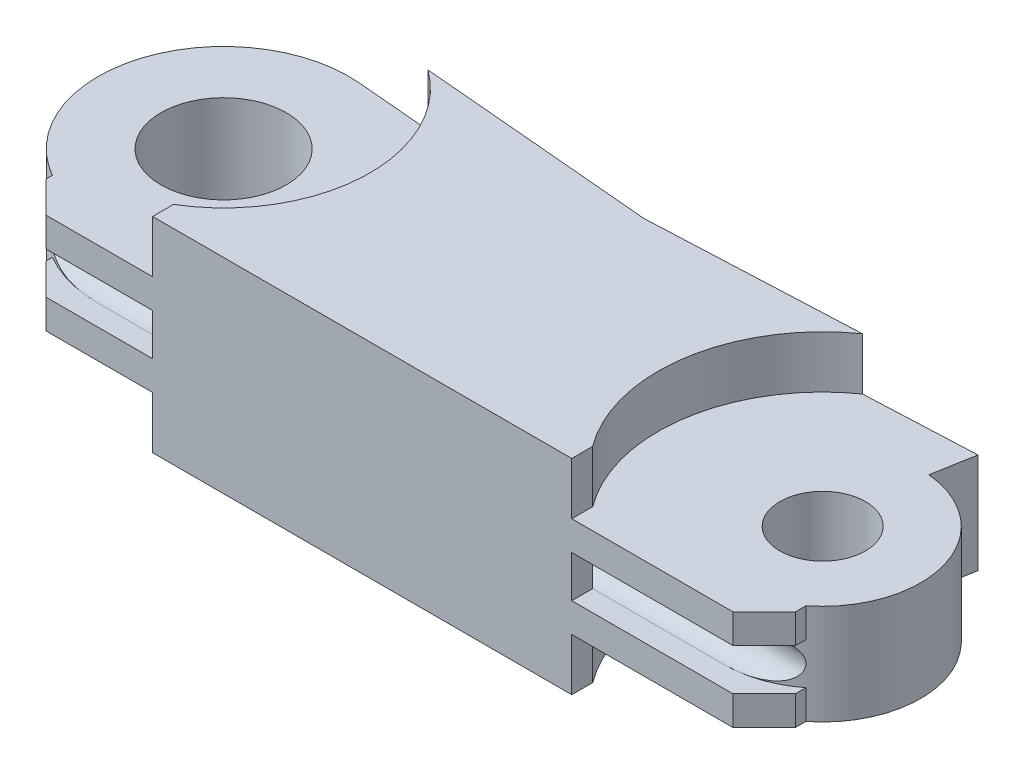
SolidWorks part; units mm, degrees
ref_plane "Front Plane" through (0, 0, 0) normal (0, 0, 1) x (1, 0, 0)
ref_plane "Top Plane" through (0, 0, 0) normal (0, 1, 0) x (1, 0, 0)
ref_plane "Right Plane" through (0, 0, 0) normal (1, 0, 0) x (0, 0, -1)
sketch "Sketch2" plane through (0, 0, 0) normal (0, 1, 0) x (1, 0, 0)
  line L0 (0, -4.6959) -> (-30, -4.6959)
  line L1 (0.4093, 4.678) -> (-29.4766, 7.2927)
  line L2 (0.4093, 4.678) -> (0.7619, 6.678)
  line L3 (0.7619, 6.678) -> (-14.5336, 5.9854)
  circle A0 centre (0, 0) radius 2.05
  arc A1 (0, -4.6959) -> (0.4093, 4.678) centre (0, 0) ccw
  circle A2 centre (-30, 1.3098) radius 3
  arc A3 (-29.4766, 7.2927) -> (-30, -4.6959) centre (-30, 1.3098) ccw
  dimension "D1" = 4.1
  dimension "D2" = 12
  dimension "D4" = 6
  dimension "D5" = 5
  dimension "D3" = 30
  dimension "D6" = 2
  dimension "D7" = 95
extrude "Boss-Extrude1" add sketch "Sketch2" along normal blind 2.4 and the other way blind 2.4 contours L1 A3 L0 A1 A0 A2 | L2 L3 L1 region at (-16.0131, 0, -0.6991) region at (-4.4541, 0, -5.7805)
sketch "Sketch10" plane through (0, 2.4, 0) normal (0, 1, 0) x (1, 0, 0)
  line L0 (-26.3929, -4.6959) -> (-6.3208, -4.6959)
  line L1 (0, -4.6959) -> (-30, -4.6959) construction
  line L3 (-25.8832, 6.9783) -> (-14.5336, 5.9854)
  line L4 (-14.5336, 5.9854) -> (-4.5336, 6.4382)
  line L5 (0.7619, 6.678) -> (-14.5336, 5.9854) construction
  line L6 (-14.5336, 5.9854) -> (-29.4766, 7.2927) construction
  line L7 (-26.3929, -4.6959) -> (-6.3208, -4.6959)
  line L8 (-26.3929, -4.6959) -> (-26.3929, -5.6959)
  line L9 (-26.3929, -5.6959) -> (-6.3208, -5.6959)
  line L10 (-6.3208, -4.6959) -> (-6.3208, -5.6959)
  circle A0 centre (0, 0) radius 4.6959
  circle A1 centre (-30, 1.3098) radius 6.0057
  arc A2 (-4.5336, 6.4382) -> (-6.3208, -4.6959) centre (0, 0) ccw
  arc A3 (-25.8832, 6.9783) -> (-26.3929, -4.6959) centre (-30, 1.3098) cw
  arc A6 (0, -4.6959) -> (0.4093, 4.678) centre (0, 0) ccw construction
  arc A7 (-29.4766, 7.2927) -> (-30, -4.6959) centre (-30, 1.3098) ccw construction
  line M3 (-14.5336, 5.9854) -> (-29.4766, 7.2927)
  line M5 (-30, -4.6959) -> (0, -4.6959)
  line M8 (0.7619, 6.678) -> (-14.5336, 5.9854)
  dimension "D1" = 1
  dimension "D3" = 10
  dimension "D2" = 1
extrude "Boss-Extrude3" add sketch "Sketch10" along normal blind 2.5 contours A3 A2 M3 M5 M8 | L10 L8 L9 M5 region at (-15.5818, 2.4, -0.85) region at (-16.3569, 2.4, 5.1959)
mirror "Mirror1" about plane through (0, 0, 0) normal (0, 1, 0) of "Boss-Extrude3"
sketch "Sketch11" plane through (0, 2.4, 0) normal (0, -1, 0) x (1, 0, 0)
  line L1 (-26.3929, 5.6959) -> (-6.3208, 5.6959)
  line L2 (-26.3929, 5.6959) -> (-26.3929, 4.6959)
  line L3 (-26.3929, 4.6959) -> (-6.3208, 4.6959)
  line L4 (-6.3208, 5.6959) -> (-6.3208, 4.6959)
extrude "Boss-Extrude4" add sketch "Sketch11" along normal up to next
sketch "Sketch13" plane through (-6.3208, 0, 0) normal (1, 0, 0) x (0, 0, -1)
  line L0 (-4.6959, -2.4) -> (-4.6959, 2.4) construction
  line L3 (-4.6959, -1) -> (-4.6959, 1)
  arc A0 (-4.6959, 1) -> (-4.6959, -1) centre (-4.6959, 0) cw
  point P0 (-4.6959, 0)
  point P7 (-4.6959, 0)
  dimension "D1" = 1
extrude "Cut-Extrude1" cut sketch "Sketch13" against normal up to next and the other way up to next
sketch "Sketch14" plane through (0, 0, 4.6959) normal (0, 0, 1) x (1, 0, 0)
  line L0 (-26.3929, -1) -> (-30, -1) construction
  line L1 (-26.3929, -2.4) -> (-33, -2.4)
  line L2 (-26.3929, -2.4) -> (-26.3929, -1)
  line L3 (-26.3929, -1) -> (-33, -1)
  line L4 (-33, -2.4) -> (-33, -1)
  line L5 (-30, -2.4) -> (-30, -1) construction
  dimension "D1" = 3
extrude "Boss-Extrude5" add sketch "Sketch14" along normal up to surface and the other way up to next up to face at (-16.3569, 0, 5.6959)
sketch "Sketch16" plane through (0, 0, 4.6959) normal (0, 0, 1) x (1, 0, 0)
  line L0 (0, -1) -> (-6.3208, -1) construction
  line L1 (-6.3208, -2.4) -> (2.8969, -2.4)
  line L2 (-6.3208, -2.4) -> (-6.3208, -1)
  line L3 (-6.3208, -1) -> (2.8969, -1)
  line L4 (2.8969, -2.4) -> (2.8969, -1)
  spline S0 degree 3 poles (0, -1) (0.2984, -1) (0.5921, -1.0011) (1.1701, -0.9919) (1.4572, -0.9819) (1.8693, -0.9245) (2.0038, -0.898) (2.2601, -0.8202) (2.3811, -0.7696) (2.6042, -0.6262) (2.7046, -0.5329) (2.8508, -0.298) (2.8967, -0.1515) (2.897, 0.1495) (2.8517, 0.2965) (2.7041, 0.5338) (2.6039, 0.6263) (2.3827, 0.7687) (2.2591, 0.8205) (2.0037, 0.898) (1.871, 0.9242) (1.4598, 0.9816) (1.1734, 0.9918) (0.5947, 1.0011) (0.2982, 1) (0, 1) knots 0 0 0 0 0.125 0.125 0.25 0.25 0.3125 0.3125 0.375 0.375 0.4375 0.4375 0.5 0.5 0.5625 0.5625 0.625 0.625 0.6875 0.6875 0.75 0.75 0.875 0.875 1 1 1 1 construction
extrude "Boss-Extrude6" add sketch "Sketch16" along normal up to surface and the other way up to next up to face at (-23.0266, -0.85, 5.6959)
chamfer "Chamfer1" distance 1.5 angle 45 2 edges at (-33, -1.7, 5.6959) (2.8969, -1.7, 5.6959)
mirror "Mirror2" about plane through (0, 0, 0) normal (0, 1, 0) of "Chamfer1", "Boss-Extrude5", "Boss-Extrude6"
equation "\"length\"= 30"
equation "\"D3@Sketch2\"=\"length\""
equation "\"height\"=12"
equation "\"D2@Sketch2\"=\"height\""
equation "\"D6@Sketch2\"=\"height\"/6"
